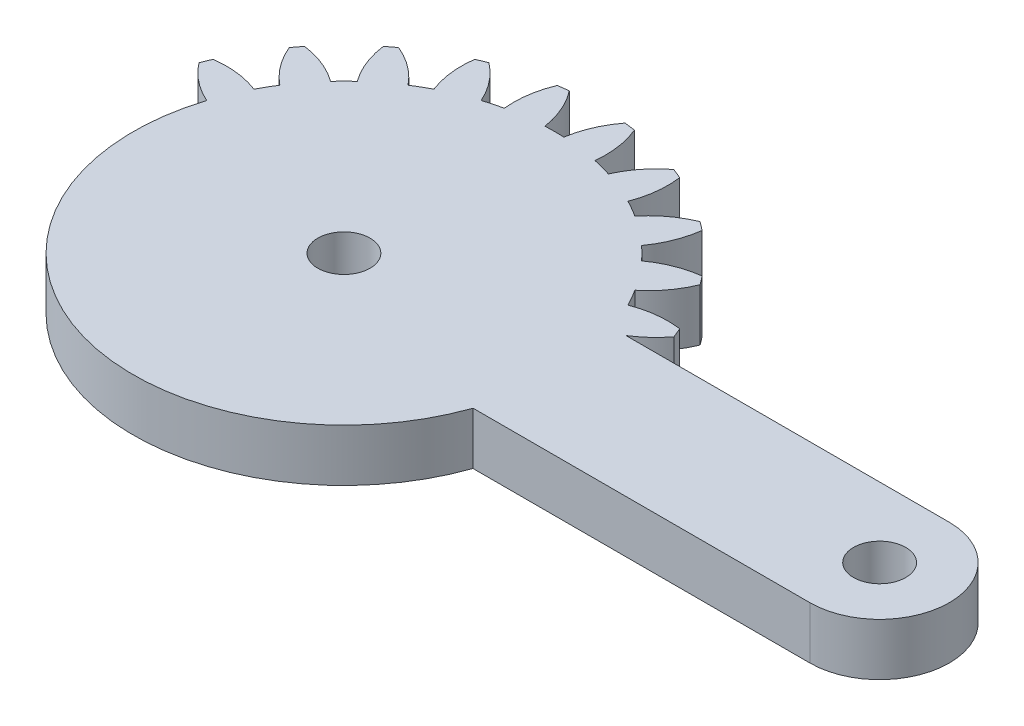
SolidWorks part; units mm, degrees
ref_plane "Front Plane" through (0, 0, 0) normal (0, 0, 1) x (1, 0, 0)
ref_plane "Top Plane" through (0, 0, 0) normal (0, 1, 0) x (1, 0, 0)
ref_plane "Right Plane" through (0, 0, 0) normal (1, 0, 0) x (0, 0, -1)
sketch "Sketch1" plane through (0, 0, 0) normal (0, 1, 0) x (1, 0, 0)
  line L0 (20.6437, 4) -> (2.0816, 4)
  line L1 (2.0816, -4) -> (20.6437, -4)
  arc A0 (2.0816, 4) -> (3.5217, 5.3071) centre (-0.7683, 8.5867) ccw
  arc A1 (3.5217, 5.3071) -> (3.2829, 5.8838) centre (-10.1063, 0) ccw
  arc A2 (3.2829, 5.8838) -> (0.6271, 5.5703) centre (2.5684, 0.5313) ccw
  arc A3 (0.6271, 5.5703) -> (0.0844, 6.5103) centre (-10.1063, 0) ccw
  arc A4 (0.0844, 6.5103) -> (1.6838, 8.6535) centre (-3.3089, 10.711) ccw
  arc A5 (1.6838, 8.6535) -> (1.3038, 9.1487) centre (-10.1063, 0) ccw
  arc A6 (1.3038, 9.1487) -> (-1.1803, 8.1585) centre (1.999, 3.7936) ccw
  arc A7 (-1.1803, 8.1585) -> (-1.9479, 8.926) centre (-10.1063, 0) ccw
  arc A8 (-1.9479, 8.926) -> (-0.9576, 11.4102) centre (-6.3127, 12.1053) ccw
  arc A9 (-0.9576, 11.4102) -> (-1.4528, 11.7901) centre (-10.1063, 0) ccw
  arc A10 (-1.4528, 11.7901) -> (-3.596, 10.1907) centre (0.6046, 6.7975) ccw
  arc A11 (-3.596, 10.1907) -> (-4.5361, 10.7334) centre (-10.1063, 0) ccw
  arc A12 (-4.5361, 10.7334) -> (-4.2225, 13.3892) centre (-9.5751, 12.6747) ccw
  arc A13 (-4.2225, 13.3892) -> (-4.7992, 13.6281) centre (-10.1063, 0) ccw
  arc A14 (-4.7992, 13.6281) -> (-6.4554, 11.5285) centre (-1.5196, 9.3381) ccw
  arc A15 (-6.4554, 11.5285) -> (-7.5039, 11.8094) centre (-10.1063, 0) ccw
  arc A16 (-7.5039, 11.8094) -> (-7.8884, 14.4558) centre (-12.8736, 12.3803) ccw
  arc A17 (-7.8884, 14.4558) -> (-8.5072, 14.5373) centre (-10.1063, 0) ccw
  arc A18 (-8.5072, 14.5373) -> (-9.5636, 12.0806) centre (-4.2291, 11.2423) ccw
  arc A19 (-9.5636, 12.0806) -> (-10.6491, 12.0806) centre (-10.1063, 0) ccw
  arc A20 (-10.6491, 12.0806) -> (-11.7054, 14.5373) centre (-15.9836, 11.2423) ccw
  arc A21 (-11.7054, 14.5373) -> (-12.3243, 14.4558) centre (-10.1063, 0) ccw
  arc A22 (-12.3243, 14.4558) -> (-12.7088, 11.8094) centre (-7.3391, 12.3803) ccw
  arc A23 (-12.7088, 11.8094) -> (-13.7573, 11.5285) centre (-10.1063, 0) ccw
  arc A24 (-13.7573, 11.5285) -> (-15.4135, 13.6281) centre (-18.6931, 9.3381) ccw
  arc A25 (-15.4135, 13.6281) -> (-15.9901, 13.3892) centre (-10.1063, 0) ccw
  arc A26 (-15.9901, 13.3892) -> (-15.6766, 10.7334) centre (-10.6376, 12.6747) ccw
  arc A27 (-15.6766, 10.7334) -> (-16.6166, 10.1907) centre (-10.1063, 0) ccw
  arc A28 (-16.6166, 10.1907) -> (-18.7599, 11.7901) centre (-20.8173, 6.7975) ccw
  arc A29 (-18.7599, 11.7901) -> (-19.255, 11.4102) centre (-10.1063, 0) ccw
  arc A30 (-19.255, 11.4102) -> (-18.2648, 8.926) centre (-13.9, 12.1053) ccw
  arc A31 (-18.2648, 8.926) -> (-19.0324, 8.1585) centre (-10.1063, 0) ccw
  arc A32 (-19.0324, 8.1585) -> (-21.5165, 9.1487) centre (-22.2117, 3.7936) ccw
  arc A33 (-21.5165, 9.1487) -> (-21.8965, 8.6535) centre (-10.1063, 0) ccw
  arc A34 (-21.8965, 8.6535) -> (-20.2971, 6.5103) centre (-16.9038, 10.711) ccw
  arc A35 (-20.2971, 6.5103) -> (-20.8398, 5.5703) centre (-10.1063, 0) ccw
  arc A36 (-20.8398, 5.5703) -> (-23.4956, 5.8838) centre (-22.7811, 0.5313) ccw
  arc A37 (-23.4956, 5.8838) -> (-23.7344, 5.3071) centre (-10.1063, 0) ccw
  arc A38 (-23.7344, 5.3071) -> (-21.6348, 3.6509) centre (-19.4444, 8.5867) ccw
  arc A39 (-21.6348, 3.6509) -> (-21.9157, 2.6025) centre (-10.1063, 0) ccw
  arc A40 (-21.9157, 2.6025) -> (-24.5622, 2.2179) centre (-22.4867, -2.7673) ccw
  arc A41 (-24.5622, 2.2179) -> (-24.6437, 1.5991) centre (-10.1063, 0) ccw
  arc A42 (-24.6437, 1.5991) -> (-22.1869, 0.5427) centre (-21.3486, 5.8773) ccw
  arc A43 (-22.1869, 0.5427) -> (-22.1869, -0.5427) centre (-10.1063, 0) ccw
  arc A44 (-22.1869, -0.5427) -> (-24.6437, -1.5991) centre (-21.3486, -5.8773) ccw
  arc A45 (-24.6437, -1.5991) -> (-24.5622, -2.2179) centre (-10.1063, 0) ccw
  arc A46 (-24.5622, -2.2179) -> (-21.9157, -2.6025) centre (-22.4867, 2.7673) ccw
  arc A47 (-21.9157, -2.6025) -> (-21.6348, -3.6509) centre (-10.1063, 0) ccw
  arc A48 (-21.6348, -3.6509) -> (-23.7344, -5.3071) centre (-19.4444, -8.5867) ccw
  arc A49 (-23.7344, -5.3071) -> (-23.4956, -5.8838) centre (-10.1063, 0) ccw
  arc A50 (-23.4956, -5.8838) -> (-20.8398, -5.5703) centre (-22.7811, -0.5313) ccw
  arc A51 (-20.8398, -5.5703) -> (-20.2971, -6.5103) centre (-10.1063, 0) ccw
  arc A52 (-20.2971, -6.5103) -> (-21.8965, -8.6535) centre (-16.9038, -10.711) ccw
  arc A53 (-21.8965, -8.6535) -> (-21.5165, -9.1487) centre (-10.1063, 0) ccw
  arc A54 (-21.5165, -9.1487) -> (-19.0324, -8.1585) centre (-22.2117, -3.7936) ccw
  arc A55 (-19.0324, -8.1585) -> (-18.2648, -8.926) centre (-10.1063, 0) ccw
  arc A56 (-18.2648, -8.926) -> (-19.255, -11.4102) centre (-13.9, -12.1053) ccw
  arc A57 (-19.255, -11.4102) -> (-18.7599, -11.7901) centre (-10.1063, 0) ccw
  arc A58 (-18.7599, -11.7901) -> (-16.6166, -10.1907) centre (-20.8173, -6.7975) ccw
  arc A59 (-16.6166, -10.1907) -> (-15.6766, -10.7334) centre (-10.1063, 0) ccw
  arc A60 (-15.6766, -10.7334) -> (-15.9901, -13.3892) centre (-10.6376, -12.6747) ccw
  arc A61 (-15.9901, -13.3892) -> (-15.4135, -13.6281) centre (-10.1063, 0) ccw
  arc A62 (-15.4135, -13.6281) -> (-13.7573, -11.5285) centre (-18.6931, -9.3381) ccw
  arc A63 (-13.7573, -11.5285) -> (-12.7088, -11.8094) centre (-10.1063, 0) ccw
  arc A64 (-12.7088, -11.8094) -> (-12.3243, -14.4558) centre (-7.3391, -12.3803) ccw
  arc A65 (-12.3243, -14.4558) -> (-11.7054, -14.5373) centre (-10.1063, 0) ccw
  arc A66 (-11.7054, -14.5373) -> (-10.6491, -12.0806) centre (-15.9836, -11.2423) ccw
  arc A67 (-10.6491, -12.0806) -> (-9.5636, -12.0806) centre (-10.1063, 0) ccw
  arc A68 (-9.5636, -12.0806) -> (-8.5072, -14.5373) centre (-4.2291, -11.2423) ccw
  arc A69 (-8.5072, -14.5373) -> (-7.8884, -14.4558) centre (-10.1063, 0) ccw
  arc A70 (-7.8884, -14.4558) -> (-7.5039, -11.8094) centre (-12.8736, -12.3803) ccw
  arc A71 (-7.5039, -11.8094) -> (-6.4554, -11.5285) centre (-10.1063, 0) ccw
  arc A72 (-6.4554, -11.5285) -> (-4.7992, -13.6281) centre (-1.5196, -9.3381) ccw
  arc A73 (-4.7992, -13.6281) -> (-4.2225, -13.3892) centre (-10.1063, 0) ccw
  arc A74 (-4.2225, -13.3892) -> (-4.5361, -10.7334) centre (-9.5751, -12.6747) ccw
  arc A75 (-4.5361, -10.7334) -> (-3.596, -10.1907) centre (-10.1063, 0) ccw
  arc A76 (-3.596, -10.1907) -> (-1.4528, -11.7901) centre (0.6046, -6.7975) ccw
  arc A77 (-1.4528, -11.7901) -> (-0.9576, -11.4102) centre (-10.1063, 0) ccw
  arc A78 (-0.9576, -11.4102) -> (-1.9479, -8.926) centre (-6.3127, -12.1053) ccw
  arc A79 (-1.9479, -8.926) -> (-1.1803, -8.1585) centre (-10.1063, 0) ccw
  arc A80 (-1.1803, -8.1585) -> (1.3038, -9.1487) centre (1.999, -3.7936) ccw
  arc A81 (1.3038, -9.1487) -> (1.6838, -8.6535) centre (-10.1063, 0) ccw
  arc A82 (1.6838, -8.6535) -> (0.0844, -6.5103) centre (-3.3089, -10.711) ccw
  arc A83 (0.0844, -6.5103) -> (0.6271, -5.5703) centre (-10.1063, 0) ccw
  arc A84 (0.6271, -5.5703) -> (3.2829, -5.8838) centre (2.5684, -0.5313) ccw
  arc A85 (3.2829, -5.8838) -> (3.5217, -5.3071) centre (-10.1063, 0) ccw
  arc A86 (3.5217, -5.3071) -> (2.0816, -4) centre (-0.7683, -8.5867) ccw
  arc A87 (20.6437, -4) -> (20.6437, 4) centre (20.6437, 0) ccw
  circle A88 centre (-10.1063, 0) radius 1.5
  circle A89 centre (20.6437, 0) radius 1.5
  dimension "D1" = 3
  dimension "D2" = 3
extrude "Boss-Extrude1" add sketch "Sketch1" along normal blind 3
sketch "Sketch2" plane through (0, 3, 0) normal (0, 1, 0) x (1, 0, 0)
  line L0 (2.0816, -4) -> (1.3057, -4)
  line L2 (20.6437, 4) -> (2.0816, 4)
  line L3 (2.0816, -4) -> (20.6437, -4)
  line L4 (20.6437, 4) -> (2.0816, 4)
  line L5 (2.0816, -4) -> (20.6437, -4)
  circle A0 centre (-10.1063, 0) radius 12.0927
  arc A88 (20.6437, -4) -> (20.6437, 4) centre (20.6437, 0) ccw
  arc A89 (2.0816, 4) -> (3.5217, 5.3071) centre (-0.7683, 8.5867) ccw
  arc A90 (3.5217, 5.3071) -> (3.2829, 5.8838) centre (-10.1063, 0) ccw
  arc A91 (3.2829, 5.8838) -> (0.6271, 5.5703) centre (2.5684, 0.5313) ccw
  arc A92 (0.6271, 5.5703) -> (0.0844, 6.5103) centre (-10.1063, 0) ccw
  arc A93 (0.0844, 6.5103) -> (1.6838, 8.6535) centre (-3.3089, 10.711) ccw
  arc A94 (1.6838, 8.6535) -> (1.3038, 9.1487) centre (-10.1063, 0) ccw
  arc A95 (1.3038, 9.1487) -> (-1.1803, 8.1585) centre (1.999, 3.7936) ccw
  arc A96 (-1.1803, 8.1585) -> (-1.9479, 8.926) centre (-10.1063, 0) ccw
  arc A97 (-1.9479, 8.926) -> (-0.9576, 11.4102) centre (-6.3127, 12.1053) ccw
  arc A98 (-0.9576, 11.4102) -> (-1.4528, 11.7901) centre (-10.1063, 0) ccw
  arc A99 (-1.4528, 11.7901) -> (-3.596, 10.1907) centre (0.6046, 6.7975) ccw
  arc A100 (-3.596, 10.1907) -> (-4.5361, 10.7334) centre (-10.1063, 0) ccw
  arc A101 (-4.5361, 10.7334) -> (-4.2225, 13.3892) centre (-9.5751, 12.6747) ccw
  arc A102 (-4.2225, 13.3892) -> (-4.7992, 13.6281) centre (-10.1063, 0) ccw
  arc A103 (-4.7992, 13.6281) -> (-6.4554, 11.5285) centre (-1.5196, 9.3381) ccw
  arc A104 (-6.4554, 11.5285) -> (-7.5039, 11.8094) centre (-10.1063, 0) ccw
  arc A105 (-7.5039, 11.8094) -> (-7.8884, 14.4558) centre (-12.8736, 12.3803) ccw
  arc A106 (-7.8884, 14.4558) -> (-8.5072, 14.5373) centre (-10.1063, 0) ccw
  arc A107 (-8.5072, 14.5373) -> (-9.5636, 12.0806) centre (-4.2291, 11.2423) ccw
  arc A108 (-9.5636, 12.0806) -> (-10.6491, 12.0806) centre (-10.1063, 0) ccw
  arc A109 (-10.6491, 12.0806) -> (-11.7054, 14.5373) centre (-15.9836, 11.2423) ccw
  arc A110 (-11.7054, 14.5373) -> (-12.3243, 14.4558) centre (-10.1063, 0) ccw
  arc A111 (-12.3243, 14.4558) -> (-12.7088, 11.8094) centre (-7.3391, 12.3803) ccw
  arc A112 (-12.7088, 11.8094) -> (-13.7573, 11.5285) centre (-10.1063, 0) ccw
  arc A113 (-13.7573, 11.5285) -> (-15.4135, 13.6281) centre (-18.6931, 9.3381) ccw
  arc A114 (-15.4135, 13.6281) -> (-15.9901, 13.3892) centre (-10.1063, 0) ccw
  arc A115 (-15.9901, 13.3892) -> (-15.6766, 10.7334) centre (-10.6376, 12.6747) ccw
  arc A116 (-15.6766, 10.7334) -> (-16.6166, 10.1907) centre (-10.1063, 0) ccw
  arc A117 (-16.6166, 10.1907) -> (-18.7599, 11.7901) centre (-20.8173, 6.7975) ccw
  arc A118 (-18.7599, 11.7901) -> (-19.255, 11.4102) centre (-10.1063, 0) ccw
  arc A119 (-19.255, 11.4102) -> (-18.2648, 8.926) centre (-13.9, 12.1053) ccw
  arc A120 (-18.2648, 8.926) -> (-19.0324, 8.1585) centre (-10.1063, 0) ccw
  arc A121 (-19.0324, 8.1585) -> (-21.5165, 9.1487) centre (-22.2117, 3.7936) ccw
  arc A122 (-21.5165, 9.1487) -> (-21.8965, 8.6535) centre (-10.1063, 0) ccw
  arc A123 (-21.8965, 8.6535) -> (-20.2971, 6.5103) centre (-16.9038, 10.711) ccw
  arc A124 (-20.2971, 6.5103) -> (-20.8398, 5.5703) centre (-10.1063, 0) ccw
  arc A125 (-20.8398, 5.5703) -> (-23.4956, 5.8838) centre (-22.7811, 0.5313) ccw
  arc A126 (-23.4956, 5.8838) -> (-23.7344, 5.3071) centre (-10.1063, 0) ccw
  arc A127 (-23.7344, 5.3071) -> (-21.6348, 3.6509) centre (-19.4444, 8.5867) ccw
  arc A128 (-21.6348, 3.6509) -> (-21.9157, 2.6025) centre (-10.1063, 0) ccw
  arc A129 (-21.9157, 2.6025) -> (-24.5622, 2.2179) centre (-22.4867, -2.7673) ccw
  arc A130 (-24.5622, 2.2179) -> (-24.6437, 1.5991) centre (-10.1063, 0) ccw
  arc A131 (-24.6437, 1.5991) -> (-22.1869, 0.5427) centre (-21.3486, 5.8773) ccw
  arc A132 (-22.1869, 0.5427) -> (-22.1869, -0.5427) centre (-10.1063, 0) ccw
  arc A133 (-22.1869, -0.5427) -> (-24.6437, -1.5991) centre (-21.3486, -5.8773) ccw
  arc A134 (-24.6437, -1.5991) -> (-24.5622, -2.2179) centre (-10.1063, 0) ccw
  arc A135 (-24.5622, -2.2179) -> (-21.9157, -2.6025) centre (-22.4867, 2.7673) ccw
  arc A136 (-21.9157, -2.6025) -> (-21.6348, -3.6509) centre (-10.1063, 0) ccw
  arc A137 (-21.6348, -3.6509) -> (-23.7344, -5.3071) centre (-19.4444, -8.5867) ccw
  arc A138 (-23.7344, -5.3071) -> (-23.4956, -5.8838) centre (-10.1063, 0) ccw
  arc A139 (-23.4956, -5.8838) -> (-20.8398, -5.5703) centre (-22.7811, -0.5313) ccw
  arc A140 (-20.8398, -5.5703) -> (-20.2971, -6.5103) centre (-10.1063, 0) ccw
  arc A141 (-20.2971, -6.5103) -> (-21.8965, -8.6535) centre (-16.9038, -10.711) ccw
  arc A142 (-21.8965, -8.6535) -> (-21.5165, -9.1487) centre (-10.1063, 0) ccw
  arc A143 (-21.5165, -9.1487) -> (-19.0324, -8.1585) centre (-22.2117, -3.7936) ccw
  arc A144 (-19.0324, -8.1585) -> (-18.2648, -8.926) centre (-10.1063, 0) ccw
  arc A145 (-18.2648, -8.926) -> (-19.255, -11.4102) centre (-13.9, -12.1053) ccw
  arc A146 (-19.255, -11.4102) -> (-18.7599, -11.7901) centre (-10.1063, 0) ccw
  arc A147 (-18.7599, -11.7901) -> (-16.6166, -10.1907) centre (-20.8173, -6.7975) ccw
  arc A148 (-16.6166, -10.1907) -> (-15.6766, -10.7334) centre (-10.1063, 0) ccw
  arc A149 (-15.6766, -10.7334) -> (-15.9901, -13.3892) centre (-10.6376, -12.6747) ccw
  arc A150 (-15.9901, -13.3892) -> (-15.4135, -13.6281) centre (-10.1063, 0) ccw
  arc A151 (-15.4135, -13.6281) -> (-13.7573, -11.5285) centre (-18.6931, -9.3381) ccw
  arc A152 (-13.7573, -11.5285) -> (-12.7088, -11.8094) centre (-10.1063, 0) ccw
  arc A153 (-12.7088, -11.8094) -> (-12.3243, -14.4558) centre (-7.3391, -12.3803) ccw
  arc A154 (-12.3243, -14.4558) -> (-11.7054, -14.5373) centre (-10.1063, 0) ccw
  arc A155 (-11.7054, -14.5373) -> (-10.6491, -12.0806) centre (-15.9836, -11.2423) ccw
  arc A156 (-10.6491, -12.0806) -> (-9.5636, -12.0806) centre (-10.1063, 0) ccw
  arc A157 (-9.5636, -12.0806) -> (-8.5072, -14.5373) centre (-4.2291, -11.2423) ccw
  arc A158 (-8.5072, -14.5373) -> (-7.8884, -14.4558) centre (-10.1063, 0) ccw
  arc A159 (-7.8884, -14.4558) -> (-7.5039, -11.8094) centre (-12.8736, -12.3803) ccw
  arc A160 (-7.5039, -11.8094) -> (-6.4554, -11.5285) centre (-10.1063, 0) ccw
  arc A161 (-6.4554, -11.5285) -> (-4.7992, -13.6281) centre (-1.5196, -9.3381) ccw
  arc A162 (-4.7992, -13.6281) -> (-4.2225, -13.3892) centre (-10.1063, 0) ccw
  arc A163 (-4.2225, -13.3892) -> (-4.5361, -10.7334) centre (-9.5751, -12.6747) ccw
  arc A164 (-4.5361, -10.7334) -> (-3.596, -10.1907) centre (-10.1063, 0) ccw
  arc A165 (-3.596, -10.1907) -> (-1.4528, -11.7901) centre (0.6046, -6.7975) ccw
  arc A166 (-1.4528, -11.7901) -> (-0.9576, -11.4102) centre (-10.1063, 0) ccw
  arc A167 (-0.9576, -11.4102) -> (-1.9479, -8.926) centre (-6.3127, -12.1053) ccw
  arc A168 (-1.9479, -8.926) -> (-1.1803, -8.1585) centre (-10.1063, 0) ccw
  arc A169 (-1.1803, -8.1585) -> (1.3038, -9.1487) centre (1.999, -3.7936) ccw
  arc A170 (1.3038, -9.1487) -> (1.6838, -8.6535) centre (-10.1063, 0) ccw
  arc A171 (1.6838, -8.6535) -> (0.0844, -6.5103) centre (-3.3089, -10.711) ccw
  arc A172 (0.0844, -6.5103) -> (0.6271, -5.5703) centre (-10.1063, 0) ccw
  arc A173 (0.6271, -5.5703) -> (3.2829, -5.8838) centre (2.5684, -0.5313) ccw
  arc A174 (3.2829, -5.8838) -> (3.5217, -5.3071) centre (-10.1063, 0) ccw
  arc A175 (3.5217, -5.3071) -> (2.0816, -4) centre (-0.7683, -8.5867) ccw
  arc A176 (20.6437, -4) -> (20.6437, 4) centre (20.6437, 0) ccw
  arc A177 (2.0816, 4) -> (3.5217, 5.3071) centre (-0.7683, 8.5867) ccw
  arc A178 (3.5217, 5.3071) -> (3.2829, 5.8838) centre (-10.1063, 0) ccw
  arc A179 (3.2829, 5.8838) -> (0.6271, 5.5703) centre (2.5684, 0.5313) ccw
  arc A180 (0.6271, 5.5703) -> (0.0844, 6.5103) centre (-10.1063, 0) ccw
  arc A181 (0.0844, 6.5103) -> (1.6838, 8.6535) centre (-3.3089, 10.711) ccw
  arc A182 (1.6838, 8.6535) -> (1.3038, 9.1487) centre (-10.1063, 0) ccw
  arc A183 (1.3038, 9.1487) -> (-1.1803, 8.1585) centre (1.999, 3.7936) ccw
  arc A184 (-1.1803, 8.1585) -> (-1.9479, 8.926) centre (-10.1063, 0) ccw
  arc A185 (-1.9479, 8.926) -> (-0.9576, 11.4102) centre (-6.3127, 12.1053) ccw
  arc A186 (-0.9576, 11.4102) -> (-1.4528, 11.7901) centre (-10.1063, 0) ccw
  arc A187 (-1.4528, 11.7901) -> (-3.596, 10.1907) centre (0.6046, 6.7975) ccw
  arc A188 (-3.596, 10.1907) -> (-4.5361, 10.7334) centre (-10.1063, 0) ccw
  arc A189 (-4.5361, 10.7334) -> (-4.2225, 13.3892) centre (-9.5751, 12.6747) ccw
  arc A190 (-4.2225, 13.3892) -> (-4.7992, 13.6281) centre (-10.1063, 0) ccw
  arc A191 (-4.7992, 13.6281) -> (-6.4554, 11.5285) centre (-1.5196, 9.3381) ccw
  arc A192 (-6.4554, 11.5285) -> (-7.5039, 11.8094) centre (-10.1063, 0) ccw
  arc A193 (-7.5039, 11.8094) -> (-7.8884, 14.4558) centre (-12.8736, 12.3803) ccw
  arc A194 (-7.8884, 14.4558) -> (-8.5072, 14.5373) centre (-10.1063, 0) ccw
  arc A195 (-8.5072, 14.5373) -> (-9.5636, 12.0806) centre (-4.2291, 11.2423) ccw
  arc A196 (-9.5636, 12.0806) -> (-10.6491, 12.0806) centre (-10.1063, 0) ccw
  arc A197 (-10.6491, 12.0806) -> (-11.7054, 14.5373) centre (-15.9836, 11.2423) ccw
  arc A198 (-11.7054, 14.5373) -> (-12.3243, 14.4558) centre (-10.1063, 0) ccw
  arc A199 (-12.3243, 14.4558) -> (-12.7088, 11.8094) centre (-7.3391, 12.3803) ccw
  arc A200 (-12.7088, 11.8094) -> (-13.7573, 11.5285) centre (-10.1063, 0) ccw
  arc A201 (-13.7573, 11.5285) -> (-15.4135, 13.6281) centre (-18.6931, 9.3381) ccw
  arc A202 (-15.4135, 13.6281) -> (-15.9901, 13.3892) centre (-10.1063, 0) ccw
  arc A203 (-15.9901, 13.3892) -> (-15.6766, 10.7334) centre (-10.6376, 12.6747) ccw
  arc A204 (-15.6766, 10.7334) -> (-16.6166, 10.1907) centre (-10.1063, 0) ccw
  arc A205 (-16.6166, 10.1907) -> (-18.7599, 11.7901) centre (-20.8173, 6.7975) ccw
  arc A206 (-18.7599, 11.7901) -> (-19.255, 11.4102) centre (-10.1063, 0) ccw
  arc A207 (-19.255, 11.4102) -> (-18.2648, 8.926) centre (-13.9, 12.1053) ccw
  arc A208 (-18.2648, 8.926) -> (-19.0324, 8.1585) centre (-10.1063, 0) ccw
  arc A209 (-19.0324, 8.1585) -> (-21.5165, 9.1487) centre (-22.2117, 3.7936) ccw
  arc A210 (-21.5165, 9.1487) -> (-21.8965, 8.6535) centre (-10.1063, 0) ccw
  arc A211 (-21.8965, 8.6535) -> (-20.2971, 6.5103) centre (-16.9038, 10.711) ccw
  arc A212 (-20.2971, 6.5103) -> (-20.8398, 5.5703) centre (-10.1063, 0) ccw
  arc A213 (-20.8398, 5.5703) -> (-23.4956, 5.8838) centre (-22.7811, 0.5313) ccw
  arc A214 (-23.4956, 5.8838) -> (-23.7344, 5.3071) centre (-10.1063, 0) ccw
  arc A215 (-23.7344, 5.3071) -> (-21.6348, 3.6509) centre (-19.4444, 8.5867) ccw
  arc A216 (-21.6348, 3.6509) -> (-21.9157, 2.6025) centre (-10.1063, 0) ccw
  arc A217 (-21.9157, 2.6025) -> (-24.5622, 2.2179) centre (-22.4867, -2.7673) ccw
  arc A218 (-24.5622, 2.2179) -> (-24.6437, 1.5991) centre (-10.1063, 0) ccw
  arc A219 (-24.6437, 1.5991) -> (-22.1869, 0.5427) centre (-21.3486, 5.8773) ccw
  arc A220 (-22.1869, 0.5427) -> (-22.1869, -0.5427) centre (-10.1063, 0) ccw
  arc A221 (-22.1869, -0.5427) -> (-24.6437, -1.5991) centre (-21.3486, -5.8773) ccw
  arc A222 (-24.6437, -1.5991) -> (-24.5622, -2.2179) centre (-10.1063, 0) ccw
  arc A223 (-24.5622, -2.2179) -> (-21.9157, -2.6025) centre (-22.4867, 2.7673) ccw
  arc A224 (-21.9157, -2.6025) -> (-21.6348, -3.6509) centre (-10.1063, 0) ccw
  arc A225 (-21.6348, -3.6509) -> (-23.7344, -5.3071) centre (-19.4444, -8.5867) ccw
  arc A226 (-23.7344, -5.3071) -> (-23.4956, -5.8838) centre (-10.1063, 0) ccw
  arc A227 (-23.4956, -5.8838) -> (-20.8398, -5.5703) centre (-22.7811, -0.5313) ccw
  arc A228 (-20.8398, -5.5703) -> (-20.2971, -6.5103) centre (-10.1063, 0) ccw
  arc A229 (-20.2971, -6.5103) -> (-21.8965, -8.6535) centre (-16.9038, -10.711) ccw
  arc A230 (-21.8965, -8.6535) -> (-21.5165, -9.1487) centre (-10.1063, 0) ccw
  arc A231 (-21.5165, -9.1487) -> (-19.0324, -8.1585) centre (-22.2117, -3.7936) ccw
  arc A232 (-19.0324, -8.1585) -> (-18.2648, -8.926) centre (-10.1063, 0) ccw
  arc A233 (-18.2648, -8.926) -> (-19.255, -11.4102) centre (-13.9, -12.1053) ccw
  arc A234 (-19.255, -11.4102) -> (-18.7599, -11.7901) centre (-10.1063, 0) ccw
  arc A235 (-18.7599, -11.7901) -> (-16.6166, -10.1907) centre (-20.8173, -6.7975) ccw
  arc A236 (-16.6166, -10.1907) -> (-15.6766, -10.7334) centre (-10.1063, 0) ccw
  arc A237 (-15.6766, -10.7334) -> (-15.9901, -13.3892) centre (-10.6376, -12.6747) ccw
  arc A238 (-15.9901, -13.3892) -> (-15.4135, -13.6281) centre (-10.1063, 0) ccw
  arc A239 (-15.4135, -13.6281) -> (-13.7573, -11.5285) centre (-18.6931, -9.3381) ccw
  arc A240 (-13.7573, -11.5285) -> (-12.7088, -11.8094) centre (-10.1063, 0) ccw
  arc A241 (-12.7088, -11.8094) -> (-12.3243, -14.4558) centre (-7.3391, -12.3803) ccw
  arc A242 (-12.3243, -14.4558) -> (-11.7054, -14.5373) centre (-10.1063, 0) ccw
  arc A243 (-11.7054, -14.5373) -> (-10.6491, -12.0806) centre (-15.9836, -11.2423) ccw
  arc A244 (-10.6491, -12.0806) -> (-9.5636, -12.0806) centre (-10.1063, 0) ccw
  arc A245 (-9.5636, -12.0806) -> (-8.5072, -14.5373) centre (-4.2291, -11.2423) ccw
  arc A246 (-8.5072, -14.5373) -> (-7.8884, -14.4558) centre (-10.1063, 0) ccw
  arc A247 (-7.8884, -14.4558) -> (-7.5039, -11.8094) centre (-12.8736, -12.3803) ccw
  arc A248 (-7.5039, -11.8094) -> (-6.4554, -11.5285) centre (-10.1063, 0) ccw
  arc A249 (-6.4554, -11.5285) -> (-4.7992, -13.6281) centre (-1.5196, -9.3381) ccw
  arc A250 (-4.7992, -13.6281) -> (-4.2225, -13.3892) centre (-10.1063, 0) ccw
  arc A251 (-4.2225, -13.3892) -> (-4.5361, -10.7334) centre (-9.5751, -12.6747) ccw
  arc A252 (-4.5361, -10.7334) -> (-3.596, -10.1907) centre (-10.1063, 0) ccw
  arc A253 (-3.596, -10.1907) -> (-1.4528, -11.7901) centre (0.6046, -6.7975) ccw
  arc A254 (-1.4528, -11.7901) -> (-0.9576, -11.4102) centre (-10.1063, 0) ccw
  arc A255 (-0.9576, -11.4102) -> (-1.9479, -8.926) centre (-6.3127, -12.1053) ccw
  arc A256 (-1.9479, -8.926) -> (-1.1803, -8.1585) centre (-10.1063, 0) ccw
  arc A257 (-1.1803, -8.1585) -> (1.3038, -9.1487) centre (1.999, -3.7936) ccw
  arc A258 (1.3038, -9.1487) -> (1.6838, -8.6535) centre (-10.1063, 0) ccw
  arc A259 (1.6838, -8.6535) -> (0.0844, -6.5103) centre (-3.3089, -10.711) ccw
  arc A260 (0.0844, -6.5103) -> (0.6271, -5.5703) centre (-10.1063, 0) ccw
  arc A261 (0.6271, -5.5703) -> (3.2829, -5.8838) centre (2.5684, -0.5313) ccw
  arc A262 (3.2829, -5.8838) -> (3.5217, -5.3071) centre (-10.1063, 0) ccw
  arc A263 (3.5217, -5.3071) -> (2.0816, -4) centre (-0.7683, -8.5867) ccw
  dimension "D1" = 0
extrude "Cut-Extrude1" cut sketch "Sketch2" against normal blind 10 contours A222 A223 A0 A221 | A226 A227 A0 A225 | A230 A231 A0 A229 | A234 A235 A0 A233 | A238 A239 A0 A237 | A242 A243 A0 A241 | A246 A247 A0 A245 | A250 A251 A0 A249 | A254 A255 A0 A253 | A258 A259 A0 A257 | A262 A263 L0 A0 A261 | A218 A219 A0 A217 region at (2.066, 3, 5.0775) region at (0.3325, 3, 8.01) region at (-2.0963, 3, 10.4389) region at (-5.071, 3, 12.1563) region at (-8.3889, 3, 13.0454) region at (-11.8238, 3, 13.0454) region at (-15.1417, 3, 12.1563) region at (-18.1164, 3, 10.4389) region at (-20.5452, 3, 8.01) region at (-22.2627, 3, 5.0353) region at (-23.1517, 3, 1.7175) region at (-23.1517, 3, -1.7175)
